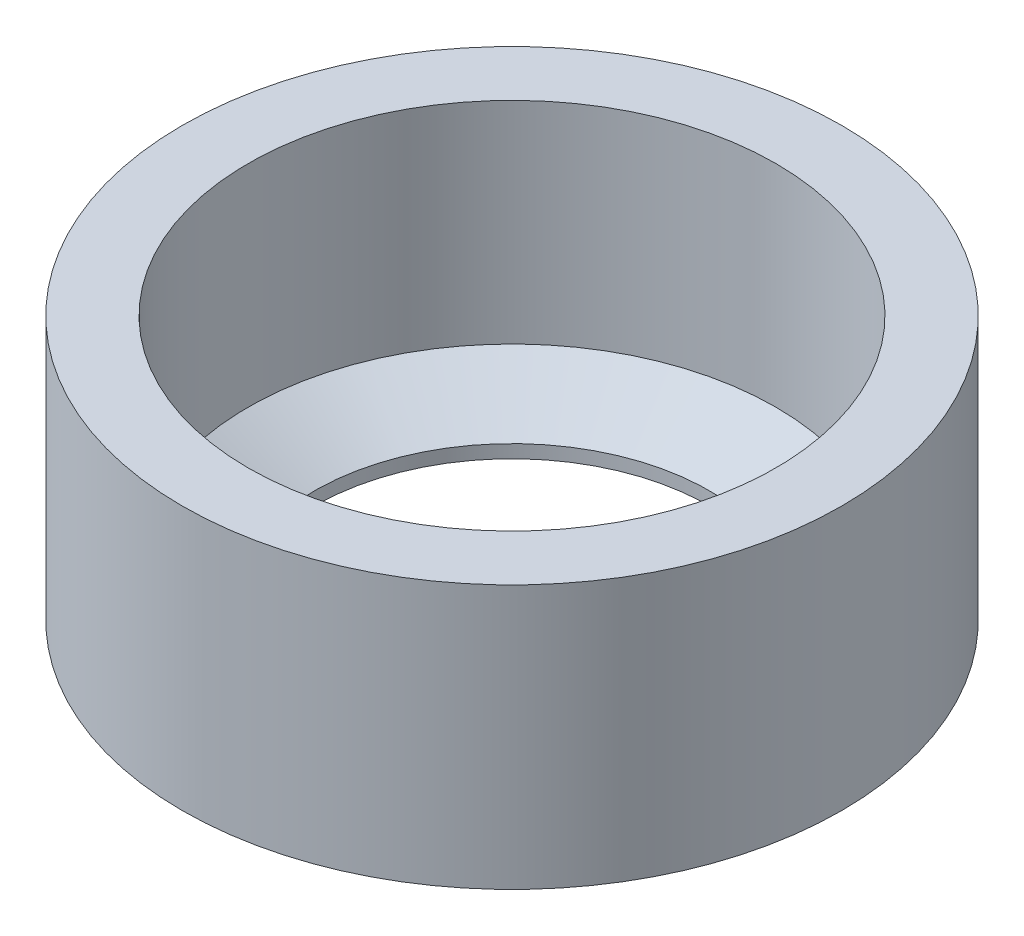
SolidWorks part; units mm, degrees
material "1023 Carbon Steel Sheet (SS)"
ref_plane "Front Plane" through (0, 0, 0) normal (0, 0, 1) x (1, 0, 0)
ref_plane "Top Plane" through (0, 0, 0) normal (0, 1, 0) x (1, 0, 0)
ref_plane "Right Plane" through (0, 0, 0) normal (1, 0, 0) x (0, 0, -1)
sketch "Sketch1" plane through (0, 0, 0) normal (0, 1, 0) x (1, 0, 0)
  circle A0 centre (0, 0) radius 15.875
  dimension "D1" = 31.75
extrude "Boss-Extrude1" add sketch "Sketch1" along normal blind 12.7
hole_wizard "1 (1) Diameter Hole1" positions "3DSketch1" profile "Sketch3" hole size "1" standard "ANSI Inch"
sketch3d "3DSketch1"
  circle A0 centre (0, 12.7, 0) radius 15.875 construction
  point P0 (0, 12.7, 0)
  point P5 (0, 28.575, 0)
  point P6 (0, 0, 0)
sketch "Sketch3" plane through (0, 12.7, 0) normal (1, 0, 0) x (0, 0, 1)
  line L0 (0, 0) -> (0, 17.7909)
  line L1 (0, 17.7909) -> (12.7, 10.16)
  line L2 (12.7, 10.16) -> (12.7, 0)
  line L5 (12.7, 0) -> (0, 0)
  line L10 (0, 17.7909) -> (-12.7, 10.16) construction
  line L11 (0, -6.35) -> (0, 107.95) construction
  dimension "Hole Dia." = 25.4
  dimension "Hole Depth" = 10.16
  dimension "Drill Angle" = 118
hole_wizard "3/4 (0.75) Diameter Hole1" positions "3DSketch2" profile "Sketch5" hole size "3/4" standard "ANSI Inch" end condition through all
sketch3d "3DSketch2"
  circle A0 centre (0, 12.7, 0) radius 12.7 construction
  point P0 (0, 12.7, 0)
  point P5 (0, 25.4, 0)
sketch "Sketch5" plane through (0, 12.7, 0) normal (1, 0, 0) x (0, 0, 1)
  line L0 (0, 0) -> (0, 12.7)
  line L1 (0, 12.7) -> (9.525, 12.7)
  line L2 (9.525, 12.7) -> (9.525, 0)
  line L5 (9.525, 0) -> (0, 0)
  line L11 (0, -6.35) -> (0, 107.95) construction
  dimension "Thru Hole Dia." = 19.05
  dimension "Thru Hole Depth" = 12.7
